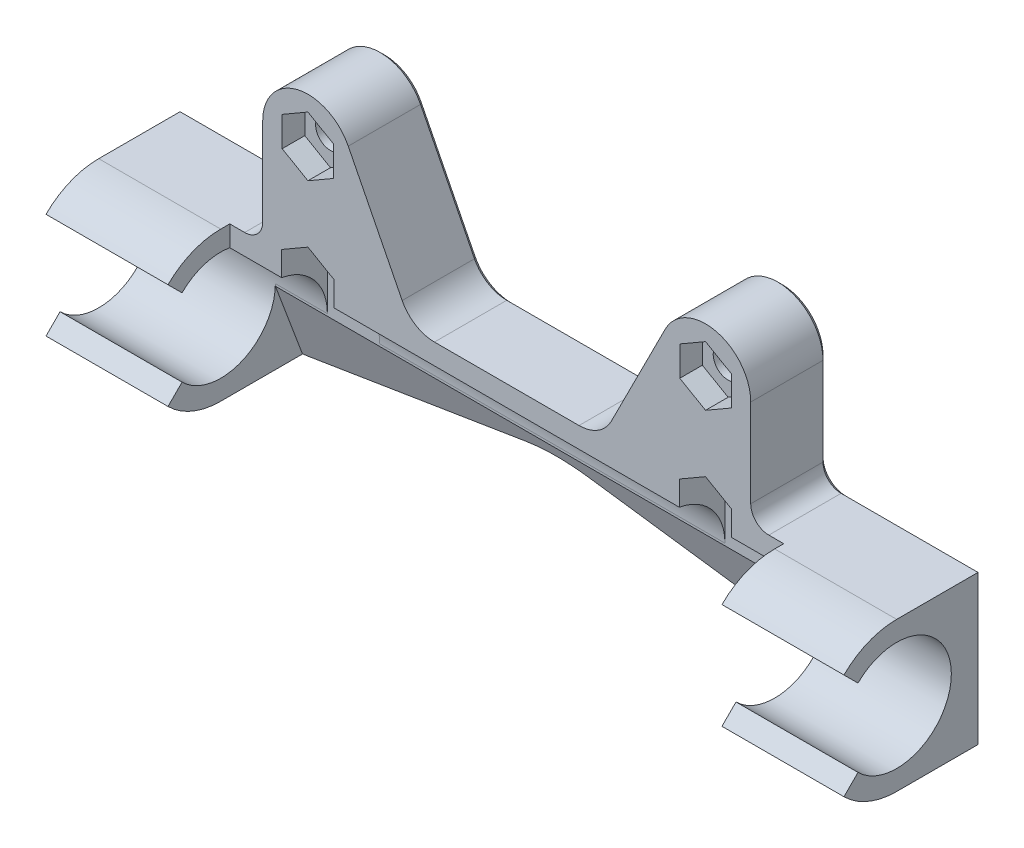
SolidWorks part; units mm, degrees
material "ABS"
ref_plane "Front Plane" through (0, 0, 0) normal (0, 0, 1) x (1, 0, 0)
ref_plane "Top Plane" through (0, 0, 0) normal (0, 1, 0) x (1, 0, 0)
ref_plane "Right Plane" through (0, 0, 0) normal (1, 0, 0) x (0, 0, -1)
sketch "Sketch1" plane through (0, 0, 0) normal (-1, 0, 0) x (0, 0, 1)
  line L0 (-9.5, 8.25) -> (-9.5, -8.25)
  line L1 (0, 8.25) -> (-9.5, 8.25)
  line L2 (0, -8.25) -> (-9.5, -8.25)
  arc A4 (0, -8.25) -> (0, 8.25) centre (0, 0) ccw
  dimension "D2" = 16.5
  dimension "D3" = 9.5
extrude "Boss-Extrude1" add sketch "Sketch1" along normal blind 88.3
hole_wizard "Ø2.7 (2.7) Diameter Hole1" [suppressed] positions "Sketch5" profile "Sketch4" hole size "Ø2.7" standard "Ansi Metric"
sketch "Sketch5" [suppressed] plane through (-9.5, 0, 0) normal (-1, 0, 0) x (0, 0, 1)
  line L1 (2.5, -5) -> (11, -5) construction
  line L2 (2.5, -5) -> (2.5, 5) construction
  line L3 (2.5, 5) -> (11, 5) construction
  line L4 (11, -5) -> (11, 5) construction
  line L5 (0, 0) -> (2.5, 0) construction
  line L7 (-8.25, 0) -> (8.25, 0) construction
  line L10 (13.5, 0) -> (11, 0) construction
  line L11 (-8.25, 13.5) -> (8.25, 13.5) construction
  point P0 (2.5, -5)
  point P89 (2.5, 5)
  point P91 (11, 5)
  point P93 (11, -5)
  dimension "D1" = 2.5
  dimension "D2" = 10
sketch "Sketch4" plane through (-9.5, -5, 2.5) normal (0, 1, 0) x (0, 0, 1)
  line L0 (0, 0) -> (0, 4.8112)
  line L1 (0, 4.8112) -> (1.35, 4)
  line L2 (1.35, 4) -> (1.35, 0)
  line L5 (1.35, 0) -> (0, 0)
  line L10 (0, 4.8112) -> (-1.35, 4) construction
  line L11 (0, -6.35) -> (0, 107.95) construction
  dimension "Hole Dia." = 2.7
  dimension "Hole Depth" = 4
  dimension "Drill Angle" = 118
sketch "Sketch6" plane through (0, 0, -9.5) normal (0, 0, -1) x (-1, 0, 0)
  line L0 (44.15, -8.25) -> (44.15, 27.1722) construction
  line L1 (88.3, -8.25) -> (0, -8.25) construction
  line L3 (17.15, -8.25) -> (17.15, 20)
  line L4 (26.6127, 22.2549) -> (32.5796, 10.4461)
  line L5 (17.15, -8.25) -> (71.15, -8.25)
  line L7 (36.1497, 8.25) -> (52.1503, 8.25)
  line L8 (88.3, 8.25) -> (0, 8.25) construction
  line L10 (61.6873, 22.2549) -> (55.7204, 10.4461)
  line L11 (71.15, -8.25) -> (71.15, 20)
  circle A0 centre (22.15, 20) radius 1.65
  arc A2 (26.6127, 22.2549) -> (17.15, 20) centre (22.15, 20) ccw
  arc A3 (32.5796, 10.4461) -> (36.1497, 8.25) centre (36.1497, 12.25) ccw
  arc A4 (55.7204, 10.4461) -> (52.1503, 8.25) centre (52.1503, 12.25) cw
  arc A5 (61.6873, 22.2549) -> (71.15, 20) centre (66.15, 20) cw
  circle A7 centre (66.15, 20) radius 1.65
  point P28 (44.15, 8.25)
  dimension "D4" = 20
  dimension "D5" = 5
  dimension "D6" = 4
extrude "Boss-Extrude2" add sketch "Sketch6" against normal blind 8.5
sketch "Sketch7" plane through (-88.3, 0, 0) normal (-1, 0, 0) x (0, 0, 1)
  line L0 (13.4819, 13.4819) -> (4.278, 4.278)
  line L1 (4.278, -4.278) -> (13.4819, -13.4819)
  line L2 (13.4819, -13.4819) -> (13.4819, 13.4819)
  line L3 (0, 0) -> (4.278, 4.278) construction
  line L4 (0, 0) -> (4.278, -4.278) construction
  arc A0 (4.278, 4.278) -> (4.278, -4.278) centre (0, 0) ccw
  dimension "D1" = 6.05
extrude "Cut-Extrude1" cut sketch "Sketch7" against normal through all
sketch "Sketch8" plane through (0, 0, -1) normal (0, 0, 1) x (1, 0, 0)
  line L0 (-88.3, 8.25) -> (0, 8.25) construction
  line L1 (-74.8, -13.234) -> (-13.5, -13.234)
  line L2 (-74.8, -13.234) -> (-74.8, 8.25)
  line L3 (-74.8, 8.25) -> (-13.5, 8.25)
  line L4 (-13.5, -13.234) -> (-13.5, 8.25)
  line L5 (-88.3, 6.05) -> (-88.3, -6.05) construction
  dimension "D1" = 13.5
  dimension "D2" = 13.5
extrude "Cut-Extrude2" cut sketch "Sketch8" along normal through all
ref_plane "Plane1" through (0, 0, -6.05) normal (0, 0, -1) x (-1, 0, 0)
sketch "Sketch9" plane through (0, 0, -6.05) normal (0, 0, -1) x (-1, 0, 0)
  line L1 (13.5, 0) -> (74.8, 0)
  line L2 (13.5, 0) -> (13.5, -11.6994)
  line L3 (13.5, -11.6994) -> (74.8, -11.6994)
  line L4 (74.8, 0) -> (74.8, -11.6994)
extrude "Cut-Extrude3" cut sketch "Sketch9" against normal through all
sketch "Sketch10" plane through (0, 0, -9.5) normal (0, 0, -1) x (-1, 0, 0)
  line L0 (22.15, 7) -> (66.15, 7) construction
  line L1 (44.15, 7) -> (44.15, -8.25) construction
  line L2 (88.3, -8.25) -> (0, -8.25) construction
  circle A0 centre (22.15, 7) radius 1.65
  circle A1 centre (66.15, 7) radius 1.65
  circle A2 centre (22.15, 20) radius 1.65 construction
  dimension "D2" = 3.3
  dimension "D1" = 44
  dimension "D3" = 13
extrude "Cut-Extrude4" cut sketch "Sketch10" against normal through all
chamfer "Chamfer1" distance 8 distance2 3 1 edges at (-44.15, -8.25, -6.05) first distance on face at (-44.15, -4.125, -6.05)
sketch "Sketch11" plane through (0, 0, -6.05) normal (0, 0, -1) x (-1, 0, 0)
  line L0 (74.8, -8.25) -> (47.5959, -1.8288)
  line L2 (40.7041, -1.8288) -> (13.5, -8.25)
  line L3 (13.5, -8.25) -> (13.5, -16.4277)
  line L4 (13.5, -16.4277) -> (74.8, -16.4277)
  line L5 (74.8, -16.4277) -> (74.8, -8.25)
  arc A0 (40.7041, -1.8288) -> (47.5959, -1.8288) centre (44.15, -16.4277) cw
  dimension "D1" = 15
extrude "Cut-Extrude5" cut sketch "Sketch11" along normal through all
fillet "Fillet1" radius 2 2 edges at (-71.15, 8.25, -5.25) (-17.15, 8.25, -5.25)
sketch "Sketch13" plane through (0, 0, -1) normal (0, 0, 1) x (1, 0, 0)
  line L1 (-69.05, -2.124) -> (-63.25, -2.124)
  line L4 (-25.05, -2.124) -> (-19.25, -2.124)
  line L7 (-66.15, 10.3486) -> (-69.05, 8.6743)
  line L8 (-69.05, 8.6743) -> (-69.05, -2.124)
  line L11 (-63.25, -2.124) -> (-63.25, 8.6743)
  line L12 (-63.25, 8.6743) -> (-66.15, 10.3486)
  line L13 (-22.15, 10.3486) -> (-25.05, 8.6743)
  line L14 (-25.05, 8.6743) -> (-25.05, -2.124)
  line L17 (-19.25, -2.124) -> (-19.25, 8.6743)
  line L18 (-19.25, 8.6743) -> (-22.15, 10.3486)
  line L19 (-69.05, 5.3257) -> (-66.15, 3.6514) [skipped]
  line L20 (-66.15, 3.6514) -> (-63.25, 5.3257) [skipped]
  line L21 (-25.05, 5.3257) -> (-22.15, 3.6514) [skipped]
  line L22 (-22.15, 3.6514) -> (-19.25, 5.3257) [skipped]
  circle A2 centre (-66.15, 7) radius 1.65 construction
  circle A3 centre (-22.15, 7) radius 1.65 construction
  circle A4 centre (-66.15, 7) radius 2.9 construction
  circle A5 centre (-22.15, 7) radius 2.9 construction
  dimension "D2" = 5.8
extrude "Cut-Extrude7" cut sketch "Sketch13" against normal up to surface (5.05 mm away) up to plane "Plane1"
sketch "Sketch14" plane through (0, 0, -1) normal (0, 0, 1) x (1, 0, 0)
  line L0 (-63.25, 8.6743) -> (-66.15, 10.3486) construction
  line L1 (-69, 21.6454) -> (-69, 18.3546)
  line L2 (-69, 18.3546) -> (-66.15, 16.7091)
  line L3 (-66.15, 16.7091) -> (-63.3, 18.3546)
  line L4 (-63.3, 18.3546) -> (-63.3, 21.6454)
  line L5 (-63.3, 21.6454) -> (-66.15, 23.2909)
  line L6 (-66.15, 23.2909) -> (-69, 21.6454)
  line L7 (-22.15, 23.2909) -> (-25, 21.6454)
  line L8 (-25, 21.6454) -> (-25, 18.3546)
  line L9 (-25, 18.3546) -> (-22.15, 16.7091)
  line L10 (-22.15, 16.7091) -> (-19.3, 18.3546)
  line L11 (-19.3, 18.3546) -> (-19.3, 21.6454)
  line L12 (-19.3, 21.6454) -> (-22.15, 23.2909)
  line L13 (-19.25, 8.6743) -> (-22.15, 10.3486) construction
  circle A0 centre (-66.15, 20) radius 2.85 construction
  circle A1 centre (-22.15, 20) radius 2.85 construction
  dimension "D1" = 5.7
  dimension "D2" = 5.7
extrude "Cut-Extrude8" cut sketch "Sketch14" against normal blind 2.5
chamfer "Chamfer2" distance 0.5 angle 45 24 edges at (0, 0, -9.5) (-6.75, -8.25, -9.5) (-27.1021, -5.0394, -9.5) (-44.15, -1.4277, -9.5) (-61.1979, -5.0394, -9.5) (-81.55, -8.25, -9.5) (-88.3, 0, -9.5) (-80.725, 8.25, -9.5) (-71.7358, 8.8358, -9.5) (-71.15, 15.125, -9.5) (-67.309, 24.8638, -9.5) (-58.7039, 16.3505, -9.5) (-54.2461, 8.843, -9.5) (-44.15, 8.25, -9.5) (-34.0539, 8.843, -9.5) (-29.5961, 16.3505, -9.5) (-20.991, 24.8638, -9.5) (-17.15, 15.125, -9.5) (-16.5642, 8.8358, -9.5) (-7.575, 8.25, -9.5) (-67.8, 7, -9.5) (-64.5, 20, -9.5) (-23.8, 20, -9.5) (-23.8, 7, -9.5)
